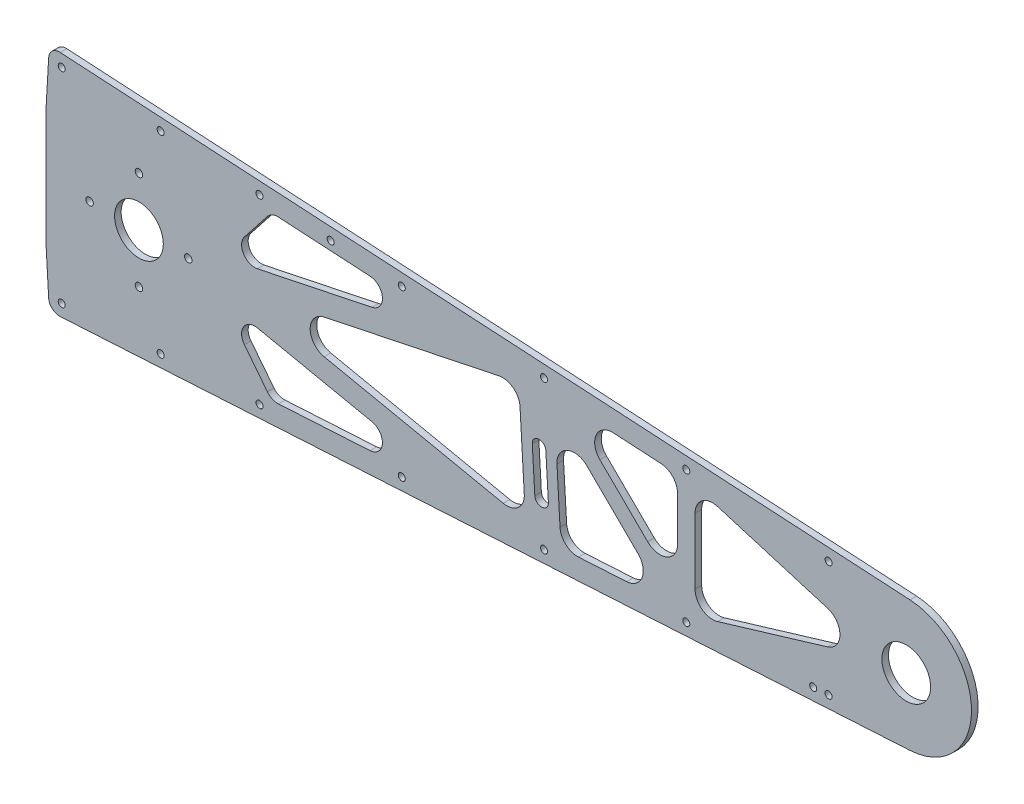
SolidWorks part; units mm, degrees
material "Thornel VCB-20 Carbon Cloth"
ref_plane "Front Plane" through (0, 0, 0) normal (0, 0, 1) x (1, 0, 0)
ref_plane "Top Plane" through (0, 0, 0) normal (0, 1, 0) x (1, 0, 0)
ref_plane "Right Plane" through (0, 0, 0) normal (1, 0, 0) x (0, 0, -1)
sketch "Sketch1" plane through (0, 0, 0) normal (0, 0, 1) x (1, 0, 0)
  line L0 (-175, 0) -> (175, 0) construction
  line L1 (-172.1122, 49.9165) -> (176.7203, 29.7354)
  line L2 (-172.1122, -49.9165) -> (176.7203, -29.7354)
  line L3 (139.566, 26.3757) -> (-120, 41.3925) construction
  line L4 (-55.1085, -37.6383) -> (9.783, -33.8841) construction
  line L5 (-125, 0) -> (-125, 62.9978) construction
  line L6 (-55.5713, 29.6383) -> (-120.4628, 33.3925) construction
  line L7 (-120.4628, 33.3925) -> (-120, 41.3925) construction
  line L8 (-55.5713, 29.6383) -> (-55.1085, 37.6383) construction
  line L9 (-88.0171, 31.5154) -> (-87.5543, 39.5154) construction
  line L10 (-120, -41.3925) -> (-165.1122, -44.0024) construction
  line L11 (139.566, -26.3757) -> (74.6745, -30.1299) construction
  circle A0 centre (175, 0) radius 11.1125
  arc A1 (176.7203, 29.7354) -> (176.7203, -29.7354) centre (175, 0) cw
  circle A3 centre (-175, 0) radius 22.5 construction
  circle A7 centre (-175, 0) radius 11.1125
  circle A9 centre (-120, 41.3925) radius 1.6
  circle A10 centre (-55.1085, 37.6383) radius 1.6
  circle A11 centre (9.783, 33.8841) radius 1.6
  circle A12 centre (74.6745, 30.1299) radius 1.6
  circle A13 centre (139.566, 26.3757) radius 1.6
  circle A15 centre (139.566, -26.3757) radius 1.6
  circle A16 centre (74.6745, -30.1299) radius 1.6
  circle A17 centre (9.783, -33.8841) radius 1.6
  circle A18 centre (-55.1085, -37.6383) radius 1.6
  circle A19 centre (-120, -41.3925) radius 1.6
  arc A20 (-172.1122, 49.9165) -> (-172.1122, -49.9165) centre (-175, 0) ccw
  circle A21 centre (-87.5543, 39.5154) radius 1.6
  circle A22 centre (-165.1122, -44.0024) radius 1.6
  circle A23 centre (-165.1122, 44.0024) radius 1.6
  circle A24 centre (132.5777, -26.78) radius 1.6
  point P4 (0, 0)
  point P18 (-175, 22.5)
  point P21 (-197.5, 0)
  point P22 (-175, -22.5)
  point P23 (-152.5, 0)
  point P30 (-88.0171, 31.5154)
  dimension "D2" = 22.225
  dimension "D3" = 50
  dimension "D5" = 45
  dimension "D6" = 3.2
  dimension "D7" = 260
  dimension "D8" = 5
  dimension "D9" = 7
  dimension "D10" = 22.225
  dimension "D11" = 7
  dimension "D16" = 5
  dimension "D1" = 350
  dimension "D4" = 8
  dimension "D12" = 5.5
extrude "Boss-Extrude1" add sketch "Sketch1" along normal blind 3
sketch "Sketch4" plane through (0, 0, 3) normal (0, 0, 1) x (1, 0, 0)
  point P10 (-197.5, 0)
  point P13 (-175, 22.5)
  point P16 (-152.5, 0)
  point P19 (-175, -22.5)
hole_wizard "M3 Clearance Hole1" positions "Sketch4" profile "Sketch6" hole size "M3" standard "ANSI Metric" end condition up to next
sketch "Sketch6" plane through (-197.5, 0, 3) normal (1, 0, 0) x (0, -1, 0)
  line L0 (0, 0) -> (0, 3)
  line L1 (0, 3) -> (1.7, 3)
  line L2 (1.7, 3) -> (1.7, 0)
  line L5 (1.7, 0) -> (0, 0)
  line L11 (0, -6.35) -> (0, 107.95) construction
  dimension "Thru Hole Dia." = 3.4
  dimension "Thru Hole Depth" = 3
sketch "Sketch7" plane through (0, 0, 3) normal (0, 0, 1) x (1, 0, 0)
  line L0 (74.6745, 30.1299) -> (74.6745, -30.1299) construction
  line L1 (74.6745, -30.1299) -> (175, 0) construction
  line L2 (175, 0) -> (74.6745, 30.1299) construction
  line L3 (175, 0) -> (-152.5, 0) construction
  line L4 (175, -29.8349) -> (175, 29.8349) construction
  line L5 (88.9755, 22.7026) -> (139.0575, 7.6619)
  line L6 (139.0575, -7.6619) -> (88.9755, -22.7026)
  line L7 (78.6745, -15.0407) -> (78.6745, 15.0407)
  line L8 (9.783, -33.8841) -> (5.5294, 39.6394) construction
  line L9 (9.783, 33.8841) -> (74.6745, -30.1299) construction
  line L10 (9.783, 33.8841) -> (74.6745, 30.1299) construction
  line L11 (9.783, -33.8841) -> (74.6745, -30.1299) construction
  line L12 (-152.5, 0) -> (-55.1085, 37.6383) construction
  line L13 (-55.1085, 37.6383) -> (9.783, 33.8841) construction
  line L14 (9.783, 33.8841) -> (-152.5, 0) construction
  line L15 (70.6745, -1.436) -> (70.6745, 18.8041)
  line L16 (63.1365, 26.7907) -> (41.3408, 28.0517)
  line L17 (35.2605, 14.3698) -> (57.0563, -7.1312)
  line L18 (29.2743, 9.0376) -> (52.6422, -14.0143)
  line L19 (47.486, -27.6962) -> (25.5253, -28.9667)
  line L20 (17.0766, -21.4421) -> (15.6694, 2.8804)
  line L21 (176.7203, 29.7354) -> (-172.1122, 49.9165) construction
  line L22 (-172.1122, -49.9165) -> (176.7203, -29.7354) construction
  line L23 (0.7692, -16.5921) -> (-1.1805, 17.1091)
  line L24 (-10.8023, 24.4781) -> (-90.5308, 7.8311)
  line L25 (-90.5308, -7.8311) -> (-8.8525, -24.8852)
  line L35 (-197.5, 0) -> (-55.1085, 37.6383) construction
  line L52 (-55.1085, -37.6383) -> (-175, -22.5) construction
  line L53 (-15.2425, -47.7117) -> (-52.5586, -43) construction
  line L54 (-0.7058, -39.4678) -> (2.1851, -39.8329) construction
  line L55 (8.6627, -14.5198) -> (7.5076, 5.4468) construction
  line L56 (5.5679, -14.6989) -> (4.4127, 5.2678)
  line L57 (11.7575, -14.3408) -> (10.6024, 5.6258)
  line L58 (176.7203, 29.7354) -> (-172.1122, 49.9165) construction
  line L59 (-175, 22.5) -> (-165.1122, 44.0024) construction
  line L60 (-152.5, 0) -> (-120, 41.3925) construction
  line L61 (-126.8967, 21.2738) -> (-116.4321, 34.6016)
  line L62 (-111.3663, 36.8863) -> (-69.5778, 34.4687)
  line L63 (-68.698, 22.6054) -> (-120.9512, 11.6951)
  line L64 (-165.9126, 32.6875) -> (-164.3288, 36.1317)
  line L65 (-158.531, 39.6149) -> (-142.9867, 38.7156)
  line L66 (-138.6141, 29.0203) -> (-146.1029, 19.4825)
  line L67 (-175.7645, 30.4115) -> (-175.2558, 31.5179)
  line L68 (-197.5, 0) -> (-225, 0) construction
  line L69 (-208.0189, 4) -> (-206.9726, 4)
  line L70 (-208.0189, -4) -> (-206.9726, -4)
  line L71 (-175.7645, -30.4115) -> (-175.2558, -31.5179)
  line L72 (-165.9126, -32.6875) -> (-164.3288, -36.1317)
  line L73 (-158.531, -39.6149) -> (-142.9867, -38.7156)
  line L74 (-138.6141, -29.0203) -> (-146.1029, -19.4825)
  line L75 (-111.3663, -36.8863) -> (-69.5778, -34.4687)
  line L76 (-126.8967, -21.2738) -> (-116.4321, -34.6016)
  line L77 (-68.698, -22.6054) -> (-120.9512, -11.6951)
  arc A0 (139.0575, 7.6619) -> (139.0575, -7.6619) centre (136.7565, 0) cw
  arc A1 (88.9755, -22.7026) -> (78.6745, -15.0407) centre (86.6745, -15.0407) cw
  arc A2 (88.9755, 22.7026) -> (78.6745, 15.0407) centre (86.6745, 15.0407) ccw
  arc A3 (70.6745, 18.8041) -> (63.1365, 26.7907) centre (62.6745, 18.8041) ccw
  arc A4 (41.3408, 28.0517) -> (35.2605, 14.3698) centre (40.8787, 20.065) ccw
  arc A5 (70.6745, -1.436) -> (57.0563, -7.1312) centre (62.6745, -1.436) cw
  arc A6 (52.6422, -14.0143) -> (47.486, -27.6962) centre (47.024, -19.7095) cw
  arc A7 (25.5253, -28.9667) -> (17.0766, -21.4421) centre (25.0632, -20.98) cw
  arc A8 (29.2743, 9.0376) -> (15.6694, 2.8804) centre (23.6561, 3.3424) ccw
  arc A9 (0.7692, -16.5921) -> (-8.8525, -24.8852) centre (-7.2174, -17.0541) cw
  arc A10 (-1.1805, 17.1091) -> (-10.8023, 24.4781) centre (-9.1672, 16.647) ccw
  arc A11 (-90.5308, 7.8311) -> (-90.5308, -7.8311) centre (-88.8957, 0) ccw
  circle A30 centre (-175, 0) radius 11.1125 construction
  circle A31 centre (-175, 0) radius 11.1125 construction
  circle A32 centre (-175, 0) radius 22.5 construction
  circle A49 centre (9.783, -33.8841) radius 1.6 construction
  circle A50 centre (9.783, -33.8841) radius 1.6
  circle A52 centre (175, 0) radius 11.1125 construction
  circle A53 centre (175, 0) radius 11.1125 construction
  arc A56 (5.5679, -14.6989) -> (11.7575, -14.3408) centre (8.6627, -14.5198) ccw
  arc A57 (10.6024, 5.6258) -> (4.4127, 5.2678) centre (7.5076, 5.4468) ccw
  circle A58 centre (-165.1122, 44.0024) radius 1.6 construction
  circle A60 centre (-120, 41.3925) radius 1.6 construction
  arc A61 (-155.1524, 19.0348) -> (-163.0653, 24.7753) centre (-175, 0) ccw
  arc A62 (-180.1025, 27.0225) -> (-201.2462, 8.209) centre (-175, 0) ccw
  arc A63 (-181.6995, 39.942) -> (-213.7614, 11.7391) centre (-175, 0) ccw
  arc A64 (-172.1122, 49.9165) -> (-172.1122, -49.9165) centre (-175, 0) ccw construction
  arc A65 (-175.2558, 31.5179) -> (-181.6995, 39.942) centre (-180.707, 34.0247) ccw
  arc A66 (-213.7614, 11.7391) -> (-208.0189, 4) centre (-208.0189, 10) ccw
  arc A67 (-201.2462, 8.209) -> (-206.9726, 4) centre (-206.9726, 10) cw
  arc A68 (-180.1025, 27.0225) -> (-175.7645, 30.4115) centre (-181.2158, 32.9183) ccw
  arc A69 (-69.5778, 34.4687) -> (-68.698, 22.6054) centre (-69.9244, 28.4787) cw
  arc A70 (-116.4321, 34.6016) -> (-111.3663, 36.8863) centre (-111.7129, 30.8963) cw
  arc A71 (-126.8967, 21.2738) -> (-120.9512, 11.6951) centre (-122.1775, 17.5685) ccw
  arc A72 (-142.9867, 38.7156) -> (-138.6141, 29.0203) centre (-143.3332, 32.7257) cw
  arc A73 (-164.3288, 36.1317) -> (-158.531, 39.6149) centre (-158.8776, 33.625) cw
  arc A74 (-163.0653, 24.7753) -> (-165.9126, 32.6875) centre (-160.4614, 30.1808) cw
  arc A75 (-155.1524, 19.0348) -> (-146.1029, 19.4825) centre (-150.822, 23.1878) ccw
  arc A76 (-213.7614, -11.7391) -> (-208.0189, -4) centre (-208.0189, -10) cw
  arc A77 (-201.2462, -8.209) -> (-206.9726, -4) centre (-206.9726, -10) ccw
  arc A78 (-180.1025, -27.0225) -> (-201.2462, -8.209) centre (-175, 0) cw
  arc A79 (-181.6995, -39.942) -> (-213.7614, -11.7391) centre (-175, 0) cw
  arc A80 (-180.1025, -27.0225) -> (-175.7645, -30.4115) centre (-181.2158, -32.9183) cw
  arc A81 (-175.2558, -31.5179) -> (-181.6995, -39.942) centre (-180.707, -34.0247) cw
  arc A82 (-164.3288, -36.1317) -> (-158.531, -39.6149) centre (-158.8776, -33.625) ccw
  arc A83 (-163.0653, -24.7753) -> (-165.9126, -32.6875) centre (-160.4614, -30.1808) ccw
  arc A84 (-155.1524, -19.0348) -> (-163.0653, -24.7753) centre (-175, 0) cw
  arc A85 (-155.1524, -19.0348) -> (-146.1029, -19.4825) centre (-150.822, -23.1878) cw
  arc A86 (-142.9867, -38.7156) -> (-138.6141, -29.0203) centre (-143.3332, -32.7257) ccw
  arc A87 (-69.5778, -34.4687) -> (-68.698, -22.6054) centre (-69.9244, -28.4787) ccw
  arc A88 (-116.4321, -34.6016) -> (-111.3663, -36.8863) centre (-111.7129, -30.8963) ccw
  arc A89 (-126.8967, -21.2738) -> (-120.9512, -11.6951) centre (-122.1775, -17.5685) cw
  point P36 (164.5699, 0)
  point P59 (-128.0368, 0)
  point P102 (-15.2425, -47.7117)
  point P126 (8.0851, -4.5365)
  dimension "D8" = 8
  dimension "D11" = 27.5
  dimension "D12" = 5
  dimension "D20" = 3.1
  dimension "D10" = 7
  dimension "D17" = 6
  dimension "D1" = 3
  dimension "D3" = 8
  dimension "D4" = 8
  dimension "D5" = 8
  dimension "D6" = 16
  dimension "D7" = 10
  dimension "D9" = 8
  dimension "D13" = 8
  dimension "D14" = 5
  dimension "D15" = 8
  dimension "D16" = 24.8967
  dimension "D22" = 20
extrude "Cut-Extrude1" cut sketch "Sketch7" against normal blind 10 contours L57 A57 L56 A56 | L24 A11 L25 A9 L23 A10 | L18 A8 L20 A7 L19 A6 | A89 L76 A88 L75 A87 L77 | L61 A71 L63 A69 L62 A70 | L20 A8 L18 A6 L19 A7 | L17 A5 L15 A3 L16 A4 | L7 A2 L5 A0 L6 A1 | L75 A87 L77 A89 L76 A88 region at (32.1755, -11.823, 3) region at (-38.9372, -0.1884, 3) region at (8.0851, -4.5365, 3) region at (-98.2756, 25.5667, 3) region at (-98.2756, -25.5667, 3)
sketch "Sketch9" [suppressed] plane through (0, 0, 3) normal (0, 0, 1) x (1, 0, 0)
  line L2 (176.7203, 29.7354) -> (-172.1122, 49.9165) construction
  line L3 (-172.1122, -49.9165) -> (176.7203, -29.7354) construction
  line L4 (254.5375, 0) -> (208, 0) construction
  line L5 (200.557, 2) -> (203.931, 2)
  line L6 (200.557, -2) -> (203.931, -2)
  line L7 (162.9445, 26.3755) -> (155.7345, 26.7926)
  line L8 (162.9445, -26.3755) -> (155.7345, -26.7926)
  arc A1 (155.7345, -26.7926) -> (155.7345, 26.7926) centre (175, 0) ccw
  arc A2 (176.7203, -29.7354) -> (176.7203, 29.7354) centre (175, 0) ccw construction
  arc A3 (200.557, -2) -> (200.557, 2) centre (175, 0) ccw
  arc A4 (162.9445, 26.3755) -> (203.931, 2) centre (175, 0) cw
  arc A5 (203.931, -2) -> (162.9445, -26.3755) centre (175, 0) cw
  dimension "D1" = 33
  dimension "D2" = 4
  dimension "D3" = 4
extrude "Boss-Extrude2" [suppressed] add sketch "Sketch9" against normal up to surface (3 mm away)
fillet "Fillet1" [suppressed] radius 1
fillet "Fillet2" [suppressed] radius 80
sketch "Sketch10" plane through (0, 0, 3) normal (0, 0, 1) x (1, 0, 0)
  line L0 (-165.1122, 44.0024) -> (-120, 41.3925) construction
  line L1 (-165.1122, 44.0024) -> (-210.2243, 46.6123) construction
  line L2 (-172.1122, 49.9165) -> (-210.905, 52.1608)
  line L3 (176.7203, 29.7354) -> (-172.1122, 49.9165) construction
  line L4 (-216.1854, 47.458) -> (-217.3977, 26.5035)
  line L5 (-172.1122, 49.9165) -> (-217.3977, 26.5035)
  circle A0 centre (-120, 41.3925) radius 1.6 construction
  circle A1 centre (-165.1122, 44.0024) radius 1.6 construction
  circle A2 centre (-210.2243, 46.6123) radius 1.6
  arc A3 (-172.1122, 49.9165) -> (-172.1122, -49.9165) centre (-175, 0) ccw construction
  arc A4 (-210.905, 52.1608) -> (-216.1854, 47.458) centre (-211.1938, 47.1692) ccw
  dimension "D2" = 5
  dimension "D1" = 6
extrude "Boss-Extrude3" add sketch "Sketch10" against normal up to surface (3 mm away) up to face at (-102.0595, -26.743, 0)
mirror "Mirror1" about plane through (0, 0, 0) normal (0, 1, 0) of "Boss-Extrude3"
sketch "Sketch11" plane through (0, 0, 0) normal (0, 0, -1) x (-1, 0, 0)
  line L0 (217.3977, -26.5035) -> (217.3977, 26.5035)
  arc A0 (217.3977, -26.5035) -> (217.3977, 26.5035) centre (175, 0) ccw construction
  arc A1 (217.3977, -26.5035) -> (217.3977, 26.5035) centre (175, 0) ccw
extrude "Cut-Extrude2" cut sketch "Sketch11" against normal through all both and the other way through all
